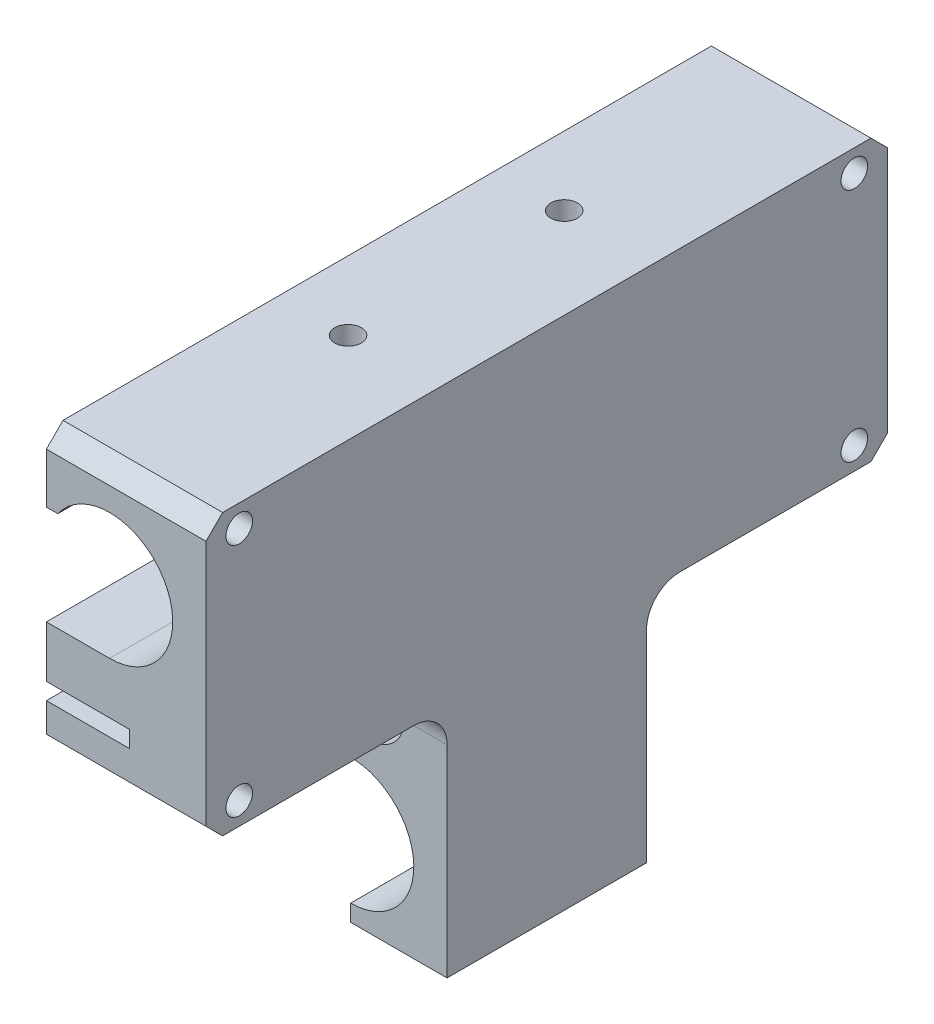
SolidWorks part; units mm, degrees
ref_plane "Front Plane" through (0, 0, 0) normal (0, 0, 1) x (1, 0, 0)
ref_plane "Top Plane" through (0, 0, 0) normal (0, 1, 0) x (1, 0, 0)
ref_plane "Right Plane" through (0, 0, 0) normal (1, 0, 0) x (0, 0, -1)
sketch "Sketch1" plane through (0, 0, 0) normal (0, 0, 1) x (1, 0, 0)
  line L0 (0, 0) -> (0, -7.6) construction
  line L1 (0, -47.6) -> (0, -49.6)
  line L2 (0, -49.6) -> (11.6, -49.6)
  line L3 (11.6, -49.6) -> (11.6, 12.4)
  line L4 (11.6, 12.4) -> (-7.6, 12.4)
  line L5 (-7.6, 12.4) -> (-7.6, 4.3592)
  line L6 (-7.6, -18.626) -> (-7.6, -9.6)
  line L8 (0, -7.6) -> (-7.6, -7.6)
  line L9 (-5.374, -34.626) -> (-7.6, -36.852)
  line L10 (-7.6, -36.852) -> (-7.6, -18.626)
  line L11 (-6.2256, 4.3592) -> (-7.6, 4.3592)
  line L13 (0, -32.4) -> (0, -40) construction
  line L14 (-7.6, -7.6) -> (-7.6, -9.6)
  arc A0 (7.6, 0) -> (0, 7.6) centre (0, 0) ccw construction
  arc A1 (0, -47.6) -> (-5.374, -34.626) centre (0, -40) ccw
  arc A2 (-7.6, -40) -> (-5.374, -34.626) centre (0, -40) ccw construction
  arc A3 (0, -7.6) -> (-6.2256, 4.3592) centre (0, 0) ccw
  dimension "D1" = 15.2
  dimension "D3" = 15.2
  dimension "D2" = 40
  dimension "D4" = 62
  dimension "D5" = 2
extrude "Boss-Extrude1" add sketch "Sketch1" along normal blind 82
ref_plane "Plane1" through (0, 0, 57) normal (0, 0, 1) x (1, 0, 0)
ref_plane "Plane2" through (0, 0, 25) normal (0, 0, -1) x (-1, 0, 0)
ref_plane "Plane3" through (0, 0, 41) normal (0, 0, -1) x (-1, 0, 0)
ref_plane "Plane4" through (0, 0, 28.5) normal (0, 0, -1) x (-1, 0, 0)
ref_plane "Plane5" through (0, 0, 53.5) normal (0, 0, -1) x (-1, 0, 0)
sketch "Sketch2" plane through (0, 0, 41) normal (0, 0, -1) x (-1, 0, 0)
  line L4 (0, -7.6) -> (7.6, -7.6) construction
  line L5 (0, -7.6) -> (7.6, -7.6)
  line L6 (0, -5) -> (7.6, -5)
  line L7 (7.6, -7.6) -> (7.6, -5)
  line L8 (6.2256, 4.3592) -> (2.449, 4.3592)
  arc A0 (6.2256, 4.3592) -> (0, -7.6) centre (0, 0) ccw construction
  arc A1 (6.2256, 4.3592) -> (0, -7.6) centre (0, 0) ccw
  arc A2 (2.449, 4.3592) -> (0, -5) centre (0, 0) ccw
extrude "Boss-Extrude2" add sketch "Sketch2" along normal blind 17 and the other way blind 17
sketch "Sketch4" plane through (-7.6, 0, 0) normal (-1, 0, 0) x (0, 0, 1)
  line L0 (0, -7.6) -> (24, -7.6) construction
  line L1 (24, 7.6) -> (24, -7.6) construction
  line L2 (54.66, -13.8) -> (82, -13.8)
  line L3 (0, 7.6) -> (0, -7.6) construction
  line L4 (0, -32.4) -> (0, -47.6) construction
  line L5 (0, -47.6) -> (82, -47.6) construction
  line L6 (82, -47.6) -> (82, -32.4) construction
  line L8 (0, -7.6) -> (24, -7.6)
  line L9 (24, 7.6) -> (24, -7.6)
  line L10 (0, 7.6) -> (24, 7.6)
  line L11 (0, 7.6) -> (0, -7.6)
  line L12 (0, -32.4) -> (0, -47.6)
  line L13 (0, -47.6) -> (82, -47.6)
  line L14 (82, -47.6) -> (82, -32.4)
  line L15 (0, -32.4) -> (82, -32.4)
  line L16 (0, 0) -> (24, 0) construction
  line L17 (0, -40) -> (82, -40)
  line L18 (-19.2091, -20) -> (91.0526, -20) construction
  line L19 (0, -13.8) -> (27.33, -13.8)
  line L20 (0, -7.6) -> (0, -36.852) construction
  line L21 (82, -7.6) -> (82, -36.852) construction
  line L22 (27.33, -13.8) -> (27.33, -15)
  line L23 (27.33, -15) -> (54.66, -15)
  line L24 (54.66, -15) -> (54.66, -13.8)
  line L25 (0, -15.8) -> (82, -15.8)
  line L26 (82, -15.8) -> (82, -13.8)
  line L27 (0, -13.8) -> (0, -15.8)
  dimension "D1" = 20
  dimension "D2" = 2
  dimension "D3" = 1.2
  dimension "D4" = 6.2
  dimension "D5" = 27.33
  dimension "D6" = 27.33
extrude "Cut-Extrude1" cut sketch "Sketch4" against normal blind 10 contours L19 L27 L25 L26 L2 L24 L23 L22 region at (-7.6, -14.6202, 68.33)
sketch "Sketch6" plane through (-7.6, 0, 0) normal (-1, 0, 0) x (0, 0, 1)
  line L0 (82, 12.4) -> (0, 12.4) construction
  line L1 (0, 12.4) -> (0, 4.3592) construction
  line L2 (0, -15.8) -> (0, -36.852) construction
  circle A0 centre (4, 9.74) radius 1.6
  circle A1 centre (4, -18.6) radius 1.6
  dimension "D1" = 3.2
  dimension "D2" = 3.2
  dimension "D3" = 2.66
  dimension "D4" = 4
  dimension "D5" = 31
  dimension "D6" = 4
extrude "Cut-Extrude2" cut sketch "Sketch6" against normal through all
mirror "Mirror1" about plane through (0, 0, 41) normal (0, 0, -1) of "Cut-Extrude2"
sketch "Sketch7" plane through (-7.6, 0, 0) normal (-1, 0, 0) x (0, 0, 1)
  line L4 (82, -36.852) -> (82, -15.8)
  line L5 (82, -15.8) -> (0, -15.8)
  line L6 (0, -15.8) -> (0, -36.852)
  line L7 (0, -36.852) -> (82, -36.852)
  line L8 (82, -29.4) -> (82, -21.3)
  line L9 (8, -21.3) -> (74, -21.3)
  line L10 (0, -21.3) -> (0, -29.4)
  line L11 (8, -21.3) -> (74, -21.3)
  line L18 (0, -21.3) -> (8, -21.3)
  line L22 (74, -21.3) -> (82, -21.3)
  line L23 (0, -29.4) -> (82, -29.4)
  line L28 (27.33, -13.8) -> (0, -13.8)
  line L29 (0, -13.8) -> (0, -15.8)
  line L30 (0, -15.8) -> (82, -15.8)
  line L31 (82, -15.8) -> (82, -13.8)
  line L32 (82, -13.8) -> (54.66, -13.8)
  line L33 (54.66, -13.8) -> (54.66, -15)
  line L34 (54.66, -15) -> (27.33, -15)
  line L35 (27.33, -15) -> (27.33, -13.8)
  line L36 (27.33, -13.8) -> (0, -13.8)
  line L37 (0, -13.8) -> (0, -15.8)
  line L38 (0, -15.8) -> (82, -15.8)
  line L39 (82, -15.8) -> (82, -13.8)
  line L40 (82, -13.8) -> (54.66, -13.8)
  line L41 (54.66, -13.8) -> (54.66, -15)
  line L42 (54.66, -15) -> (27.33, -15)
  line L43 (27.33, -15) -> (27.33, -13.8)
  circle A0 centre (4, -18.6) radius 1.6 construction
  circle A1 centre (78, -18.6) radius 1.6 construction
  circle A2 centre (4, -18.6) radius 1.6
  line M5 (82, -36.852) -> (82, -15.8)
  line M7 (0, -15.8) -> (0, -36.852)
  dimension "D4" = 2.7
  dimension "D6" = 2.7
  dimension "D2" = 0
  dimension "D1" = 0
extrude "Cut-Extrude3" cut sketch "Sketch7" against normal blind 14 contours L23 L22 L9 L18 M7 M5 region at (-7.6, -25.35, 41)
chamfer "Chamfer1" distance 2 angle 45 2 edges at (2, 12.4, 82) (2, 12.4, 0)
sketch "Sketch9" plane through (-7.6, 0, 0) normal (-1, 0, 0) x (0, 0, 1)
  line L1 (82, -49.6) -> (0, -49.6) construction
  line L2 (82, -21.3) -> (82, -49.6)
  line L4 (0, -21.3) -> (82, -21.3) construction
  line L5 (29, -21.3) -> (29, -49.6)
  line L6 (53, -21.3) -> (53, -49.6)
  line L7 (41, 10.56) -> (41, -10.56) construction
  line L8 (82, -49.6) -> (53, -49.6)
  line L9 (0, -21.3) -> (29, -21.3)
  line L10 (53, -21.3) -> (82, -21.3)
  line L11 (29, -49.6) -> (0, -49.6)
  line L12 (0, -21.3) -> (0, -49.6)
  dimension "D1" = 12
  dimension "D2" = 12
extrude "Cut-Extrude4" cut sketch "Sketch9" against normal through all
fillet "Fillet1" radius 4 2 edges at (6.4, -29.4, 41) (6.4, -21.3, 41)
fillet "Fillet2" radius 4 2 edges at (7, -21.3, 53) (7, -21.3, 29)
chamfer "Chamfer2" distance 2 angle 45 2 edges at (2, -21.3, 82) (2, -21.3, 0)
sketch "Sketch10" plane through (-7.6, 0, 0) normal (-1, 0, 0) x (0, 0, 1)
  line L0 (0, 7.6) -> (0, -7.6) construction
  line L1 (29, -32.4) -> (29, -47.6) construction
  line L2 (0, 7.6) -> (0, -7.6)
  line L3 (29, -32.4) -> (29, -47.6)
  line L5 (29, -40) -> (54.0404, -40)
chamfer "Chamfer3" distance 5 angle 45 1 edges at (-7.6, -29.4, 41)
fillet "Fillet3" radius 4 2 edges at (-7.6, -34.4, 41) (-2.6, -29.4, 41)
sketch "Sketch11" plane through (0, 2.3963, 0) normal (0, -1, 0) x (1, 0, 0)
  circle A0 centre (0.6872, 54) radius 1.6
extrude "Cut-Extrude5" cut sketch "Sketch11" along normal up to next from surface contours A0 region at (0.6872, 2.3963, 54) starting at face at (2, 12.4, 41)
mirror "Mirror2" about plane through (0, 0, 41) normal (0, 0, -1) of "Cut-Extrude5"
sketch "Sketch12" plane through (0, 2.3963, 0) normal (0, -1, 0) x (1, 0, 0)
  line L1 (-2.0841, 52.4) -> (0.6872, 50.8)
  line L2 (0.6872, 50.8) -> (3.4585, 52.4)
  line L3 (3.4585, 52.4) -> (3.4585, 55.6)
  line L4 (3.4585, 55.6) -> (0.6872, 57.2)
  line L5 (0.6872, 57.2) -> (-2.0841, 55.6)
  line L6 (-2.0841, 55.6) -> (-2.0841, 52.4)
  circle A0 centre (0.6872, 54) radius 3.2 construction
  dimension "D1" = 6.4
extrude "Cut-Extrude6" cut sketch "Sketch12" against normal blind 5
mirror "Mirror3" about plane through (0, 0, 41) normal (0, 0, -1) of "Cut-Extrude6"
